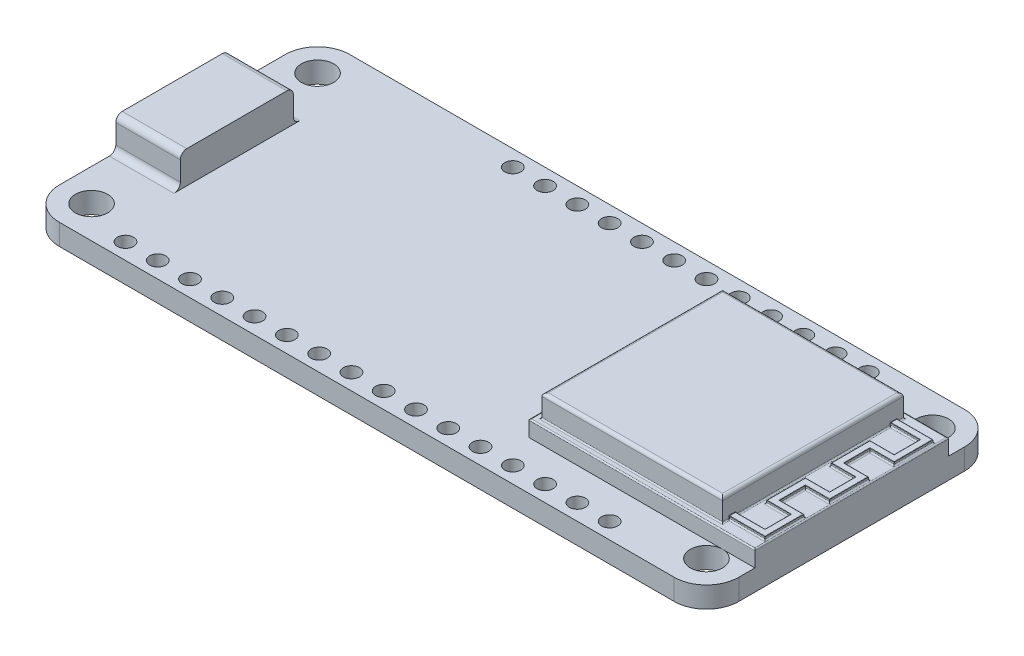
SolidWorks part; units mm, degrees
ref_plane "Front Plane" through (0, 0, 0) normal (0, 0, 1) x (1, 0, 0)
ref_plane "Top Plane" through (0, 0, 0) normal (0, 1, 0) x (1, 0, 0)
ref_plane "Right Plane" through (0, 0, 0) normal (1, 0, 0) x (0, 0, -1)
sketch "Sketch1" plane through (0, 0, 0) normal (0, 1, 0) x (1, 0, 0)
  line L1 (24.1935, -11.43) -> (-24.1935, -11.43)
  line L2 (26.7335, -8.89) -> (26.7335, 8.89)
  line L3 (24.1935, 11.43) -> (-24.1935, 11.43)
  line L4 (-26.7335, -8.89) -> (-26.7335, 8.89)
  line L5 (26.7335, -11.43) -> (-26.7335, 11.43) construction
  line L6 (26.7335, 11.43) -> (-26.7335, -11.43) construction
  circle A0 centre (-24.1935, 8.89) radius 1.27
  circle A1 centre (24.1935, 8.89) radius 1.27
  circle A2 centre (24.1935, -8.89) radius 1.27
  circle A3 centre (-24.1935, -8.89) radius 1.27
  circle A4 centre (17.8435, -10.16) radius 0.635
  circle A5 centre (15.3035, -10.16) radius 0.635
  circle A6 centre (12.7635, -10.16) radius 0.635
  circle A7 centre (10.2235, -10.16) radius 0.635
  circle A8 centre (7.6835, -10.16) radius 0.635
  circle A9 centre (5.1435, -10.16) radius 0.635
  circle A10 centre (2.6035, -10.16) radius 0.635
  circle A11 centre (0.0635, -10.16) radius 0.635
  circle A12 centre (-2.4765, -10.16) radius 0.635
  circle A13 centre (-5.0165, -10.16) radius 0.635
  circle A14 centre (-7.5565, -10.16) radius 0.635
  circle A15 centre (-10.0965, -10.16) radius 0.635
  circle A16 centre (-12.6365, -10.16) radius 0.635
  circle A17 centre (-15.1765, -10.16) radius 0.635
  circle A18 centre (-17.7165, -10.16) radius 0.635
  circle A19 centre (-20.2565, -10.16) radius 0.635
  circle A20 centre (17.8435, 10.16) radius 0.635
  circle A21 centre (15.3035, 10.16) radius 0.635
  circle A22 centre (12.7635, 10.16) radius 0.635
  circle A23 centre (10.2235, 10.16) radius 0.635
  circle A24 centre (7.6835, 10.16) radius 0.635
  circle A25 centre (5.1435, 10.16) radius 0.635
  circle A26 centre (2.6035, 10.16) radius 0.635
  circle A27 centre (0.0635, 10.16) radius 0.635
  circle A28 centre (-2.4765, 10.16) radius 0.635
  circle A29 centre (-5.0165, 10.16) radius 0.635
  circle A30 centre (-7.5565, 10.16) radius 0.635
  circle A31 centre (-10.0965, 10.16) radius 0.635
  arc A32 (24.1935, -11.43) -> (26.7335, -8.89) centre (24.1935, -8.89) ccw
  arc A33 (26.7335, 8.89) -> (24.1935, 11.43) centre (24.1935, 8.89) ccw
  arc A34 (-24.1935, 11.43) -> (-26.7335, 8.89) centre (-24.1935, 8.89) ccw
  arc A35 (-24.1935, -11.43) -> (-26.7335, -8.89) centre (-24.1935, -8.89) cw
  point P0 (0, 0)
  dimension "D3" = 2.54
  dimension "D8" = 2.54
  dimension "D10" = 1.27
  dimension "D16" = 1.27
  dimension "D20" = 2.54
  dimension "D1" = 53.467
  dimension "D2" = 22.86
  dimension "D4" = 2.54
  dimension "D5" = 2.54
  dimension "D9" = 2.54
  dimension "D11" = 1.27
  dimension "D12" = 8.89
  dimension "D14" = 1.27
  dimension "D15" = 8.89
  dimension "D18" = 48.387
  dimension "D19" = 17.78
  dimension "D6" = 2
  dimension "D7" = 2
  dimension "D13" = 16
  dimension "D17" = 12
extrude "Boss-Extrude1" add sketch "Sketch1" along normal blind 1.651
sketch "Sketch6" plane through (0, 1.651, 0) normal (0, 1, 0) x (1, 0, 0)
  line L0 (-26.7335, 8.89) -> (-26.7335, -8.89) construction
  line L1 (-26.7335, -4.445) -> (-21.6535, -4.445)
  line L2 (-26.7335, -4.445) -> (-26.7335, 4.445)
  line L3 (-26.7335, 4.445) -> (-21.6535, 4.445)
  line L4 (-21.6535, -4.445) -> (-21.6535, 4.445)
  point P6 (-26.7335, 0)
  dimension "D1" = 8.89
  dimension "D2" = 5.08
extrude "Boss-Extrude8" add sketch "Sketch6" along normal blind 2.54
sketch "Sketch7" plane through (-26.7335, 0, 0) normal (-1, 0, 0) x (0, 0, 1)
  line L0 (-4.445, 2.921) -> (4.445, 2.921) construction
  line L3 (-4.445, 4.191) -> (-4.445, 1.651) construction
  line L11 (4.445, 4.191) -> (4.445, 1.651) construction
  line L12 (0, 4.191) -> (0, 0) construction
  line L13 (-4.445, 4.191) -> (4.445, 4.191) construction
  line L14 (-8.89, 0) -> (8.89, 0) construction
  line L15 (3.81, 3.8569) -> (-3.81, 3.8569)
  line L16 (2.54, 1.9851) -> (-2.54, 1.9851)
  line L17 (-2.54, 1.9851) -> (-3.81, 3.8569)
  line L18 (3.81, 3.8569) -> (2.54, 1.9851)
  point P12 (-3.175, 2.921)
  point P15 (0, 3.8569)
  point P18 (0, 1.9851)
  point P19 (3.175, 2.921)
  dimension "D1" = 7.62
  dimension "D2" = 5.08
extrude "Cut-Extrude1" cut sketch "Sketch7" against normal blind 2.54
fillet "Fillet1" radius 0.508 4 edges at (-24.1935, 4.191, 4.445) (-24.1935, 1.651, 4.445) (-24.1935, 4.191, -4.445) (-24.1935, 1.651, -4.445)
fillet "Fillet2" radius 0.254 4 edges at (-25.4635, 1.9851, 2.54) (-25.4635, 1.9851, -2.54) (-25.4635, 3.8569, -3.81) (-25.4635, 3.8569, 3.81)
sketch "Sketch9" plane through (0, 1.651, 0) normal (0, 1, 0) x (1, 0, 0)
  line L0 (26.7335, 0) -> (-21.6535, 0) construction
  line L1 (26.7335, -8.89) -> (26.7335, 8.89) construction
  line L2 (-21.6535, -4.953) -> (-21.6535, 4.953) construction
  line L4 (8.9535, -7.62) -> (26.7335, -7.62)
  line L5 (8.9535, -7.62) -> (8.9535, 7.62)
  line L6 (8.9535, 7.62) -> (26.7335, 7.62)
  line L7 (26.7335, -7.62) -> (26.7335, 7.62)
  line L8 (8.9535, -7.62) -> (26.7335, 7.62) construction
  line L9 (8.9535, 7.62) -> (26.7335, -7.62) construction
  point P6 (17.8435, 0)
  dimension "D1" = 15.24
  dimension "D2" = 17.78
extrude "Boss-Extrude9" add sketch "Sketch9" along normal blind 1.27
sketch "Sketch10" plane through (0, 2.921, 0) normal (0, 1, 0) x (1, 0, 0)
  line L0 (8.9535, 0) -> (26.7335, 0) construction
  line L1 (8.9535, 7.62) -> (8.9535, -7.62) construction
  line L2 (26.7335, -7.62) -> (26.7335, 7.62) construction
  line L3 (26.7335, 7.62) -> (8.9535, 7.62) construction
  line L4 (23.6855, -7.112) -> (9.4615, -7.112)
  line L5 (23.6855, -7.112) -> (23.6855, 7.112)
  line L6 (23.6855, 7.112) -> (9.4615, 7.112)
  line L7 (9.4615, -7.112) -> (9.4615, 7.112)
  line L8 (23.6855, -7.112) -> (9.4615, 7.112) construction
  line L9 (23.6855, 7.112) -> (9.4615, -7.112) construction
  point P6 (16.5735, 0)
  dimension "D1" = 0.508
  dimension "D2" = 0.508
extrude "Boss-Extrude10" add sketch "Sketch10" along normal blind 1.778
sketch "Sketch11" plane through (0, 2.921, 0) normal (0, 1, 0) x (1, 0, 0)
  line L0 (23.6855, -6.35) -> (26.261, -6.35) construction
  line L1 (23.6855, -7.112) -> (23.6855, 7.112) construction
  line L2 (26.261, -6.35) -> (26.261, -3.81)
  line L3 (26.261, -3.81) -> (24.356, -3.81)
  line L4 (24.356, -3.81) -> (24.356, -1.27) construction
  line L5 (24.356, -1.27) -> (26.261, -1.27) construction
  line L6 (26.261, -1.27) -> (26.261, 1.27) construction
  line L7 (26.261, 1.27) -> (24.356, 1.27) construction
  line L8 (24.356, 1.27) -> (24.356, 3.81) construction
  line L9 (24.356, 3.81) -> (26.261, 3.81) construction
  line L10 (26.261, 3.81) -> (26.261, 6.35) construction
  line L11 (26.261, 6.35) -> (23.6855, 6.35) construction
  line L12 (26.7335, 7.62) -> (8.9535, 7.62) construction
  line L13 (24.1935, -7.62) -> (26.7335, -7.62) construction
  line L14 (23.6855, -6.604) -> (26.515, -6.604)
  line L15 (26.515, -6.604) -> (26.515, -3.556)
  line L16 (26.515, -3.556) -> (24.61, -3.556)
  line L17 (24.61, -3.556) -> (24.61, -1.524)
  line L18 (24.61, -1.524) -> (26.515, -1.524)
  line L19 (26.515, -1.524) -> (26.515, 1.524)
  line L20 (26.515, 1.524) -> (24.61, 1.524)
  line L21 (24.61, 1.524) -> (24.61, 3.556)
  line L22 (24.61, 3.556) -> (26.515, 3.556)
  line L23 (26.515, 3.556) -> (26.515, 6.604)
  line L24 (26.515, 6.604) -> (23.6855, 6.604)
  line L25 (23.6855, -6.096) -> (26.007, -6.096)
  line L26 (26.007, -6.096) -> (26.007, -4.064)
  line L27 (26.007, -4.064) -> (24.102, -4.064)
  line L28 (24.102, -4.064) -> (24.102, -1.016)
  line L29 (24.102, -1.016) -> (26.007, -1.016)
  line L30 (26.007, -1.016) -> (26.007, 1.016)
  line L31 (26.007, 1.016) -> (24.102, 1.016)
  line L32 (24.102, 1.016) -> (24.102, 4.064)
  line L33 (24.102, 4.064) -> (26.007, 4.064)
  line L34 (26.007, 4.064) -> (26.007, 6.096)
  line L35 (26.007, 6.096) -> (23.6855, 6.096)
  line L36 (23.6855, -6.604) -> (23.6855, -6.096)
  line L37 (23.6855, 6.604) -> (23.6855, 6.096)
  dimension "D1" = 1.27
  dimension "D2" = 1.27
  dimension "D3" = 1.905
  dimension "D4" = 0.254
  dimension "D5" = 0.254
extrude "Boss-Extrude11" add sketch "Sketch11" along normal blind 0.254 contours L35 L34 L33 L32 L31 L30 L29 L28 L27 L26 L25 L14 L15 L16 L17 L18 L19 L20 L21 L22 L23 L24 region at (23.8206, 2.921, 6.35)
fillet "Fillet3" radius 0.254 4 edges at (16.5735, 4.699, -7.112) (23.6855, 4.699, 0) (16.5735, 4.699, 7.112) (9.4615, 4.699, 0)
fillet "Fillet4" radius 0.0254 28 edges at (23.6855, 3.048, -6.604) (23.6855, 3.048, -6.096) (23.6855, 3.048, 6.604) (23.6855, 3.048, 6.096) (23.6855, 3.175, -6.35) (25.1003, 3.175, -6.604) (26.515, 3.175, -5.08) (25.5625, 3.175, -3.556) (24.61, 3.175, -2.54) (25.5625, 3.175, -1.524) (26.515, 3.175, 0) (25.5625, 3.175, 1.524) (24.61, 3.175, 2.54) (25.5625, 3.175, 3.556) (26.515, 3.175, 5.08) (25.1003, 3.175, 6.604) (23.6855, 3.175, 6.35) (24.8463, 3.175, 6.096) (26.007, 3.175, 5.08) (25.0545, 3.175, 4.064) (24.102, 3.175, 2.54) (25.0545, 3.175, 1.016) (26.007, 3.175, 0) (25.0545, 3.175, -1.016) (24.102, 3.175, -2.54) (25.0545, 3.175, -4.064) (26.007, 3.175, -5.08) (24.8463, 3.175, -6.096)
fillet "Fillet6" radius 0.1016 36 edges at (26.007, 2.921, -5.08) (25.0545, 2.921, -4.064) (24.102, 2.921, -2.54) (25.0545, 2.921, -1.016) (26.007, 2.921, 0) (25.0545, 2.921, 1.016) (24.102, 2.921, 2.54) (25.0545, 2.921, 4.064) (26.007, 2.921, 5.08) (24.859, 2.921, 6.096) (23.6929, 2.921, 6.0886) (23.6855, 2.921, 0) (23.6929, 2.921, -6.0886) (24.859, 2.921, -6.096) (16.5735, 2.921, -7.112) (9.4615, 2.921, 0) (16.5735, 2.921, 7.112) (23.6855, 2.921, 6.8707) (23.6929, 2.921, 6.6114) (25.113, 2.921, 6.604) (26.515, 2.921, 5.08) (25.5625, 2.921, 3.556) (24.61, 2.921, 2.54) (25.5625, 2.921, 1.524) (26.515, 2.921, 0) (25.5625, 2.921, -1.524) (24.61, 2.921, -2.54) (25.5625, 2.921, -3.556) (26.515, 2.921, -5.08) (25.113, 2.921, -6.604) (23.6929, 2.921, -6.6114) (23.6855, 2.921, -6.8707) (17.8435, 2.921, 7.62) (8.9535, 2.921, 0) (17.8435, 2.921, -7.62) (26.7335, 2.921, 0)
